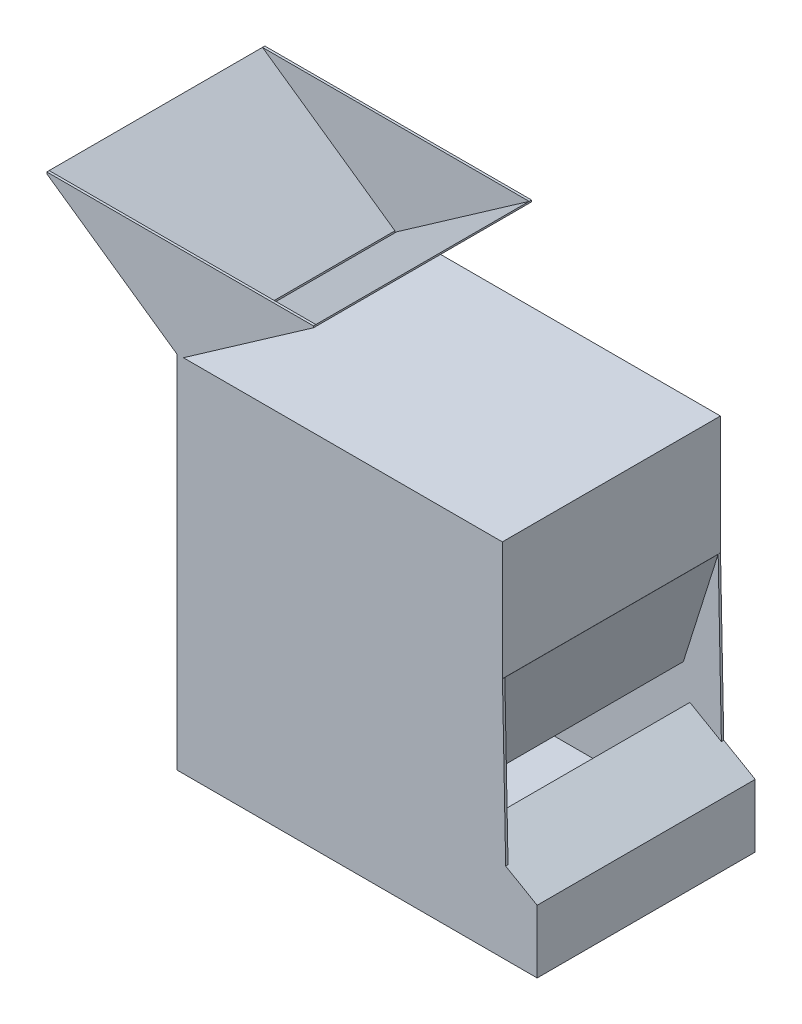
SolidWorks part; units mm, degrees
note: The reader was unsure of these and kept them because the rebuilt part matched: shared geometry of "草图8<3>".
ref_plane "前视基准面" through (0, 0, 0) normal (0, 0, 1) x (1, 0, 0)
ref_plane "上视基准面" through (0, 0, 0) normal (0, 1, 0) x (1, 0, 0)
ref_plane "右视基准面" through (0, 0, 0) normal (1, 0, 0) x (0, 0, -1)
sketch "草图1" plane through (0, 0, 0) normal (0, 0, 1) x (1, 0, 0)
  line L0 (0, 0) -> (0, 200)
  line L1 (0, 200) -> (270, 200)
  line L3 (248.2424, 79.8823) -> (300, 50)
  line L4 (300, 50) -> (300, 0)
  line L5 (300, 0) -> (0, 0)
  line L6 (270, 200) -> (241.7969, 110.613)
  line L7 (-2, 202) -> (272.7282, 202)
  line L8 (272.7282, 202) -> (243.338, 108.8504)
  line L10 (-2, 202) -> (-2, -2)
  line L11 (-2, -2) -> (302, -2)
  line L12 (302, -2) -> (302, 51.1547)
  line L13 (302, 51.1547) -> (248.8665, 81.8314)
  circle A0 centre (220, 90) radius 30
  dimension "D6" = 60
  dimension "D1" = 300
  dimension "D2" = 200
  dimension "D3" = 50
  dimension "D4" = 30
  dimension "D5" = 270
  dimension "D7" = 110
  dimension "225" = 220
  dimension "D8" = 72.489
  dimension "D9" = 2
  dimension "D10" = 2
  dimension "D11" = 2
  dimension "D12" = 2
  dimension "D13" = 2
  dimension "D14" = 2
extrude "凸台-拉伸3" add sketch "草图1" along normal blind 180 contours A0 L8 L7 L10 L11 L12 L13 L3 L4 L5 L0 L1 L6
sketch "草图7" plane through (0, 0, 0) normal (0, 0, -1) x (-1, 0, 0)
  line L0 (-272.7282, 202) -> (-275.4332, 66.493)
  line L1 (-302, 51.1547) -> (-248.8665, 81.8314) construction
  line L2 (-275.4332, 66.493) -> (-302, 51.1547)
  line L3 (-302, 51.1547) -> (-302, -2)
  line L4 (-302, -2) -> (2, -2)
  line L5 (2, -2) -> (2, 202)
  line L6 (2, 202) -> (-272.7282, 202)
extrude "凸台-拉伸4" add sketch "草图7" along normal blind 2 contours L3 L4 L5 L6 L0 L2
ref_plane "基准面3" through (0, 0, 90) normal (0, 0, 1) x (1, 0, 0)
mirror "镜向5" about plane through (0, 0, 90) normal (0, 0, 1) of "凸台-拉伸4"
sketch "草图8" plane through (0, 0, 0) normal (0, 0, 1) x (1, 0, 0)
  line L0 (272.7282, 202) -> (243.338, 108.8504) construction
  line L1 (-2, 202) -> (272.7282, 202) construction
  line L2 (-2, 202) -> (-2, -2) construction
  line L3 (-2, -2) -> (302, -2) construction
  line L4 (302, -2) -> (302, 51.1547) construction
  line L5 (302, 51.1547) -> (248.8665, 81.8314) construction
  line L6 (270, 200) -> (241.7969, 110.613) construction
  line L7 (0, 200) -> (270, 200) construction
  line L8 (0, 0) -> (0, 200) construction
  line L9 (300, 0) -> (0, 0) construction
  line L10 (300, 50) -> (300, 0) construction
  line L11 (248.2424, 79.8823) -> (300, 50) construction
  line L12 (272.7282, 202) -> (243.338, 108.8504) construction
  line L13 (-2, 202) -> (272.7282, 202) construction
  line L14 (-2, 202) -> (-2, -2) construction
  line L15 (-2, -2) -> (302, -2) construction
  line L16 (302, -2) -> (302, 51.1547) construction
  line L17 (302, 51.1547) -> (248.8665, 81.8314) construction
  line L18 (270, 200) -> (241.7969, 110.613) construction
  line L19 (0, 200) -> (270, 200)
  line L20 (0, 0) -> (0, 200) construction
  line L21 (300, 0) -> (0, 0) construction
  line L22 (300, 50) -> (300, 0) construction
  line L23 (248.2424, 79.8823) -> (300, 50) construction
  line L24 (220, 135.3561) -> (220, 31.0609) construction
  line L25 (165.6053, 90) -> (270, 90) construction
  line L26 (212.2354, 118.9778) -> (220, 90) construction
  line L27 (227.7646, 118.9778) -> (220, 90) construction
  line L28 (248.9778, 97.7646) -> (220, 90) construction
  line L29 (241.2132, 111.2132) -> (220, 90) construction
  line L30 (241.2132, 68.7868) -> (220, 90) construction
  line L31 (248.9778, 82.2354) -> (220, 90) construction
  line L32 (212.2354, 61.0222) -> (220, 90) construction
  line L33 (227.7646, 61.0222) -> (220, 90) construction
  line L34 (191.0222, 82.2354) -> (220, 90) construction
  line L35 (198.7868, 68.7868) -> (220, 90) construction
  line L36 (198.7868, 111.2132) -> (220, 90) construction
  line L37 (191.0222, 97.7646) -> (220, 90) construction
  line L38 (191.0222, 97.7646) -> (0, 144.3277)
  line L39 (0, 0) -> (0, 200) construction
  line L40 (0, 140.3998) -> (190.2705, 94.0199)
  line L41 (270, 200) -> (270.631, 202)
  line L42 (270.631, 202) -> (0, 202)
  line L43 (0, 202) -> (0, 200)
  circle A0 centre (220, 90) radius 30
  circle A1 centre (220, 90) radius 30
  circle A2 centre (220, 90) radius 30 construction
  point P36 (220, 90)
  dimension "D2" = 30
  dimension "D1" = 0
  dimension "D3" = 6
extrude "凸台-拉伸5" add sketch "草图8" along normal blind 180
sketch "草图10" plane through (0, 0, 0) normal (0, 0, 1) x (1, 0, 0)
  line L0 (300, 0) -> (0, 0) construction
  line L1 (0, 0) -> (0, 200) construction
  circle A0 centre (60, 60) radius 2.5
  circle A1 centre (95, 60) radius 6
  dimension "D1" = 5
  dimension "D4" = 35
  dimension "D5" = 12
  dimension "D2" = 60
  dimension "D3" = 60
extrude "切除-拉伸8" cut sketch "草图10" along normal blind 6 and the other way blind 14
extrude "切除-拉伸9" cut sketch "草图8<3>" along normal blind 180 contours L19 L41 L42 L43
sketch "草图8<3>" plane through (0, 0, 0) normal (0, 0, 1) x (1, 0, 0) same geometry as "草图8"
sketch "草图11" plane through (0, 202, 0) normal (0, 1, 0) x (1, 0, 0)
  line L0 (0, 0) -> (0, -180)
  line L1 (0, -180) -> (270.631, -180)
  line L2 (270.631, -180) -> (270.631, 0)
  line L3 (270.631, 0) -> (0, 0)
extrude "拉伸-薄壁1" add sketch "草图11" along normal blind 100 thin thin type one direction wall 2
sketch "草图12" plane through (0, 0, 180) normal (0, 0, -1) x (-1, 0, 0)
  line L0 (-1.5, 302) -> (-1.5, 272)
  line L1 (-272.631, 302) -> (2, 302) construction
  line L2 (-1.5, 272) -> (-1, 262)
  line L4 (0, 144.3277) -> (0, 302) construction
  line L5 (-1.5, 302) -> (-3.5, 302)
  line L6 (-3.5, 302) -> (-3.5, 272)
  line L7 (-3.5, 272) -> (-1, 262)
  point P4 (0, 0)
  dimension "D1" = 1.5
  dimension "D2" = 0.5
  dimension "D3" = 30
  dimension "D4" = 2
  dimension "D6" = 10
extrude "凸台-拉伸6" add sketch "草图12" along normal up to next
sketch "草图13" plane through (0, 0, 180) normal (0, 0, -1) x (-1, 0, 0)
  line L0 (0, 302) -> (-1.5, 302) construction
  line L1 (-0.75, 328.8965) -> (-0.75, 289.6242) construction
  line L2 (-1.5, 302) -> (-113.2688, 380.1482)
  line L3 (-3.5, 302) -> (-113.2688, 378.7498)
  line L4 (-113.2688, 378.7498) -> (-113.2688, 380.1482)
  line L5 (-1.5, 302) -> (-3.5, 302)
  line L6 (111.7688, 378.7498) -> (111.7688, 380.1482)
  line L7 (0, 302) -> (2, 302)
  line L8 (2, 302) -> (111.7688, 378.7498)
  line L9 (0, 302) -> (111.7688, 380.1482)
extrude "凸台-拉伸7" add sketch "草图13" along normal blind 180
sketch "草图14" plane through (0, 0, 0) normal (0, 0, -1) x (-1, 0, 0)
  line L0 (-113.2688, 380.1482) -> (111.7688, 380.1482)
  line L1 (111.7688, 380.1482) -> (111.7688, 378.7498)
  line L2 (111.7688, 378.7498) -> (2, 302)
  line L3 (2, 302) -> (-3.5, 302)
  line L4 (-3.5, 302) -> (-113.2688, 378.7498)
  line L5 (-113.2688, 378.7498) -> (-113.2688, 380.1482)
extrude "凸台-拉伸8" add sketch "草图14" along normal blind 2
mirror "镜向6" about plane through (0, 0, 90) normal (0, 0, 1) of "凸台-拉伸8"
sketch "草图15" plane through (0, 0, 180) normal (0, 0, -1) x (-1, 0, 0)
  line L0 (-270.631, 302) -> (-270.631, 300)
  line L1 (-270.631, 302) -> (-270.631, 202) construction
  line L2 (-270.631, 300) -> (-3.5, 300)
  line L3 (-3.5, 302) -> (-3.5, 272) construction
  line L4 (-3.5, 300) -> (-3.5, 302)
  line L5 (-3.5, 302) -> (-270.631, 302)
  dimension "D1" = 2
extrude "凸台-拉伸9" add sketch "草图15" along normal up to next
